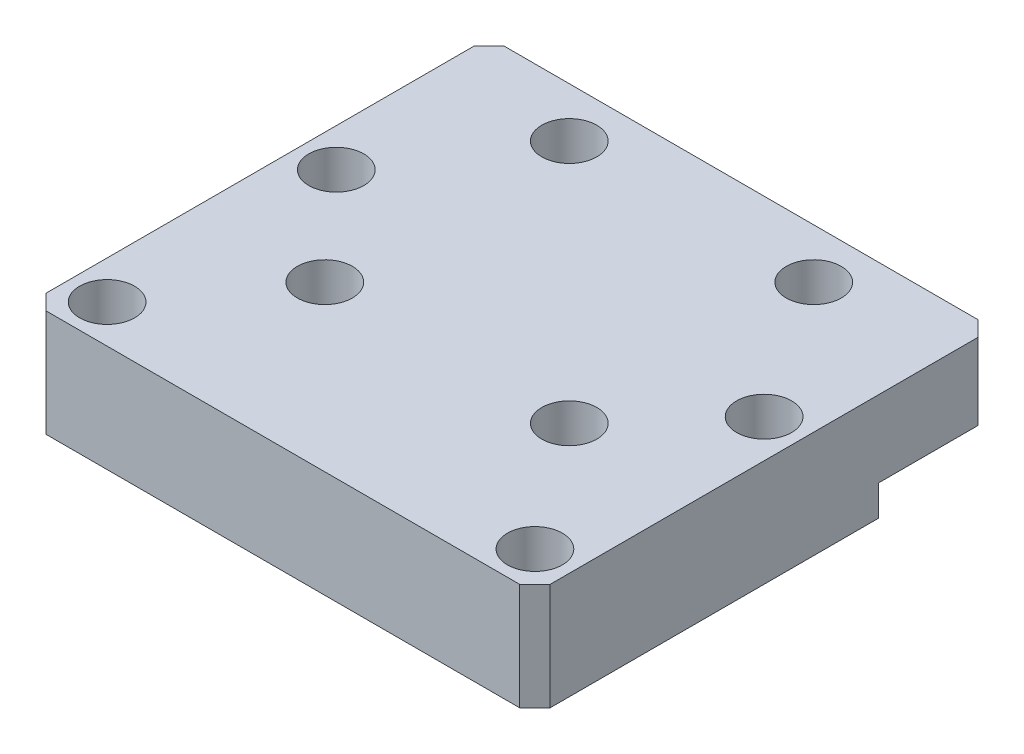
SolidWorks part; units mm, degrees
material "6061 Alloy"
ref_plane "Front Plane" through (0, 0, 0) normal (0, 0, 1) x (1, 0, 0)
ref_plane "Top Plane" through (0, 0, 0) normal (0, 1, 0) x (1, 0, 0)
ref_plane "Right Plane" through (0, 0, 0) normal (1, 0, 0) x (0, 0, -1)
sketch "Sketch1" plane through (0, 0, 0) normal (0, 1, 0) x (1, 0, 0)
  line L1 (16.5, -11.25) -> (-16.5, -11.25)
  line L2 (16.5, -11.25) -> (16.5, 11.25)
  line L3 (16.5, 11.25) -> (-16.5, 11.25)
  line L4 (-16.5, -11.25) -> (-16.5, 11.25)
  line L5 (16.5, -11.25) -> (-16.5, 11.25) construction
  line L6 (16.5, 11.25) -> (-16.5, -11.25) construction
  point P0 (0, 0)
  dimension "D1" = 22.5
  dimension "D2" = 33
extrude "Boss-Extrude1" add sketch "Sketch1" along normal blind 7
sketch "Sketch2" plane through (0, 7, 0) normal (0, 1, 0) x (1, 0, 0)
  line L1 (-16.5, -11.25) -> (16.5, -11.25) construction
  line L2 (0, 11.25) -> (0, -11.25) construction
  line L3 (16.5, 11.25) -> (-16.5, 11.25) construction
  point P0 (-14, 6.25)
  point P1 (-14, -8.75)
  point P2 (14, -8.75)
  point P3 (14, 6.25)
  dimension "D1" = 28
  dimension "D2" = 15
  dimension "D3" = 2.5
hole_wizard "M3 Clearance Hole1" positions "3DSketch1" profile "Sketch3" hole size "M3" standard "GB" end condition through all
sketch3d "3DSketch1"
  point P0 (-14, 7, -6.25)
  point P3 (14, 7, -6.25)
  point P6 (14, 7, 8.75)
  point P9 (-14, 7, 8.75)
sketch "Sketch3" plane through (-14, 7, -6.25) normal (1, 0, 0) x (0, 0, 1)
  line L0 (0, 0) -> (0, 7)
  line L1 (0, 7) -> (1.8, 7)
  line L2 (1.8, 7) -> (1.8, 0)
  line L5 (1.8, 0) -> (0, 0)
  line L11 (0, -6.35) -> (0, 107.95) construction
  dimension "Thru Hole Dia." = 3.6
  dimension "Thru Hole Depth" = 7
sketch "Sketch4" plane through (0, 0, 0) normal (0, -1, 0) x (1, 0, 0)
  line L0 (-8, 0.5) -> (8, -15.5) construction
  line L3 (0, -11.25) -> (0, 11.25) construction
  point P0 (-8, 0.5)
  point P4 (0, -7.5)
  point P8 (8, 0.5)
  point P9 (8, -15.5)
  point P10 (-8, -15.5)
  dimension "D1" = 16
  dimension "D2" = 16
  dimension "D3" = 7.5
sketch "Sketch7" plane through (0, 0, 0) normal (0, -1, 0) x (1, 0, 0)
  line L0 (0, -11.25) -> (0, 11.25) construction
  line L1 (16.5, -11.25) -> (-16.5, -11.25) construction
  line L2 (-14.6059, -11.25) -> (0, 7.7847)
  line L3 (0, -3.85) -> (0, 3.85) construction
  line L4 (14.6059, -11.25) -> (0, 7.7847)
  point P0 (0, -1.25)
  dimension "D1" = 1.25
  dimension "D2" = 75
  dimension "D3" = 5.5
extrude "Cut-Extrude1" cut sketch "Sketch7" against normal blind 2 and the other way through all
sketch "Sketch8" plane through (0, 2, 0) normal (0, -1, 0) x (1, 0, 0)
  line L1 (-16.5, -11.25) -> (16.5, -11.25)
  line L2 (-16.5, -11.25) -> (-16.5, -18.75)
  line L3 (-16.5, -18.75) -> (16.5, -18.75)
  line L4 (16.5, -11.25) -> (16.5, -18.75)
  dimension "D1" = 7.5
extrude "Boss-Extrude2" add sketch "Sketch8" against normal up to surface (5 mm away) up to face at (-14, 7, -4.45)
fillet "Fillet1" radius 5.5 1 edges at (0, 1, 7.7847)
chamfer "Chamfer1" distance 1 angle 45 4 edges at (-16.5, 3.5, 11.25) (16.5, 3.5, 11.25) (16.5, 4.5, -18.75) (-16.5, 4.5, -18.75)
hole_wizard "CBORE for M3 Hexagon socket head cap screws1" positions "3DSketch2" profile "Sketch5" counterbore size "M3" standard "GB" end condition through all
sketch3d "3DSketch2"
  point P0 (-8, 0, 0.5)
  point P3 (8, 0, 0.5)
  point P6 (-8, 0, -15.5)
  point P9 (8, 0, -15.5)
sketch "Sketch5" plane through (-8, 0, 0.5) normal (1, 0, 0) x (0, 0, -1)
  line L0 (0, 0) -> (0, 7)
  line L1 (0, 7) -> (1.8, 7)
  line L3 (1.8, 7) -> (1.8, 4.4)
  line L4 (1.8, 4.4) -> (3, 4.4)
  line L5 (3, 4.4) -> (3, 0)
  line L7 (3, 0) -> (0, 0)
  line L11 (0, -6.35) -> (0, 107.95) construction
  dimension "Thru Hole Dia." = 3.6
  dimension "Thru Hole Depth" = 7
  dimension "C'Bore Dia." = 6
  dimension "C'Bore Depth" = 4.4
fillet "Fillet2" radius 2 4 edges at (7.8902, 1, -2.498) (5.0757, 1, 1.1699) (-5.0757, 1, 1.1699) (-7.8902, 1, -2.498)
